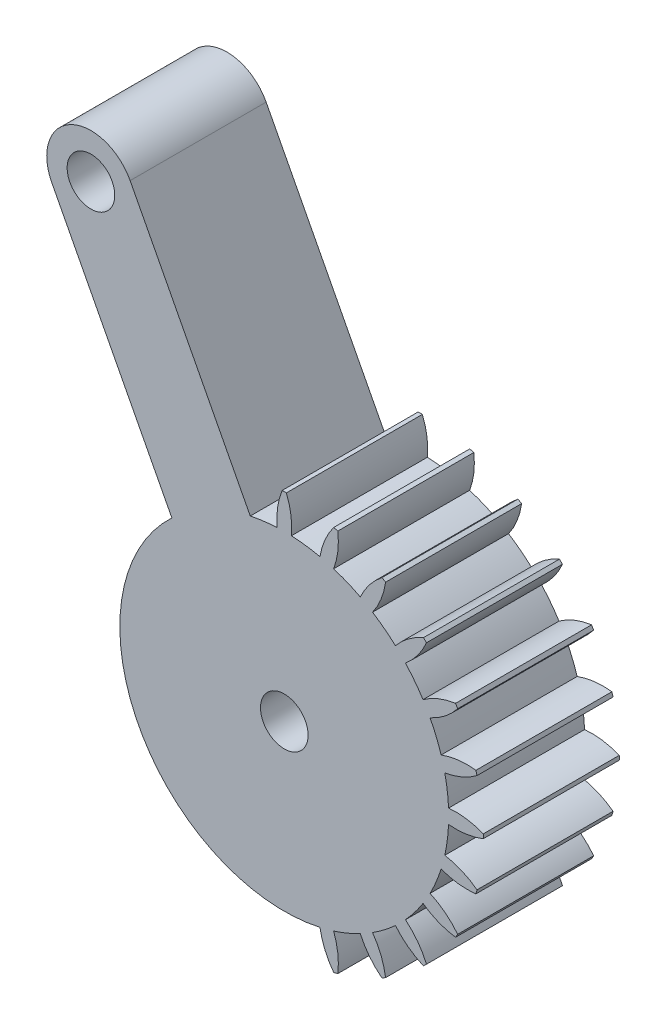
SolidWorks part; units mm, degrees
ref_plane "Front Plane" through (0, 0, 0) normal (0, 0, 1) x (1, 0, 0)
ref_plane "Top Plane" through (0, 0, 0) normal (0, 1, 0) x (1, 0, 0)
ref_plane "Right Plane" through (0, 0, 0) normal (1, 0, 0) x (0, 0, -1)
sketch "Sketch1" plane through (0, 0, 0) normal (0, 0, 1) x (1, 0, 0)
  line L0 (0, 0) -> (0, 16.3128) construction
  line L1 (0.155, 14.63) -> (-0.155, 14.63)
  line L2 (0, 0) -> (-14.3268, 27.4806) construction
  line L3 (3.9362, 14.0914) -> (3.6368, 14.1716)
  line L4 (7.4492, 12.5925) -> (7.1808, 12.7475)
  line L5 (10.4546, 10.2354) -> (10.2354, 10.4546)
  line L6 (12.7475, 7.1808) -> (12.5925, 7.4492)
  line L7 (14.1716, 3.6368) -> (14.0914, 3.9362)
  line L8 (14.63, -0.155) -> (14.63, 0.155)
  line L9 (14.0914, -3.9362) -> (14.1716, -3.6368)
  line L10 (12.5925, -7.4492) -> (12.7475, -7.1808)
  line L11 (10.2354, -10.4546) -> (10.4546, -10.2354)
  line L12 (7.1808, -12.7475) -> (7.4492, -12.5925)
  line L13 (3.6368, -14.1716) -> (3.9362, -14.0914)
  line L14 (0, 0) -> (0.52, 12.0788) construction
  line L15 (0, 0) -> (3.6285, 11.5327) construction
  line L16 (-2.5015, 11.8284) -> (-11.3335, 28.7694)
  line L17 (-8.2652, 8.8235) -> (-17.0973, 25.7645)
  circle A0 centre (0, 0) radius 1.75
  arc A1 (-8.2652, 8.8235) -> (2.6239, -11.8018) centre (0, 0) ccw
  arc A2 (-11.3335, 28.7694) -> (-17.0973, 25.7645) centre (-14.2154, 27.2669) ccw
  circle A3 centre (-14.2154, 27.2669) radius 1.75
  arc A4 (-0.155, 14.63) -> (-0.52, 12.0788) centre (4.8536, 12.6117) ccw
  arc A5 (0.155, 14.63) -> (0.52, 12.0788) centre (-4.8536, 12.6117) cw
  arc A6 (3.9362, 14.0914) -> (3.6285, 11.5327) centre (-1.4241, 13.4382) cw
  arc A7 (3.6368, 14.1716) -> (2.6239, 11.8018) centre (7.9524, 10.9258) ccw
  arc A8 (7.4492, 12.5925) -> (6.4897, 10.2006) centre (2.1025, 13.3489) cw
  arc A9 (7.1808, 12.7475) -> (5.5891, 10.7206) centre (10.5092, 8.4952) ccw
  arc A10 (10.4546, 10.2354) -> (8.9087, 8.1733) centre (5.4858, 12.3499) cw
  arc A11 (10.2354, 10.4546) -> (8.1733, 8.9087) centre (12.3499, 5.4858) ccw
  arc A12 (12.7475, 7.1808) -> (10.7206, 5.5891) centre (8.4952, 10.5092) cw
  arc A13 (12.5925, 7.4492) -> (10.2006, 6.4897) centre (13.3489, 2.1025) ccw
  arc A14 (14.1716, 3.6368) -> (11.8018, 2.6239) centre (10.9258, 7.9524) cw
  arc A15 (14.0914, 3.9362) -> (11.5327, 3.6285) centre (13.4382, -1.4241) ccw
  arc A16 (14.63, -0.155) -> (12.0788, -0.52) centre (12.6117, 4.8536) cw
  arc A17 (14.63, 0.155) -> (12.0788, 0.52) centre (12.6117, -4.8536) ccw
  arc A18 (14.0914, -3.9362) -> (11.5327, -3.6285) centre (13.4382, 1.4241) cw
  arc A19 (14.1716, -3.6368) -> (11.8018, -2.6239) centre (10.9258, -7.9524) ccw
  arc A20 (12.5925, -7.4492) -> (10.2006, -6.4897) centre (13.3489, -2.1025) cw
  arc A21 (12.7475, -7.1808) -> (10.7206, -5.5891) centre (8.4952, -10.5092) ccw
  arc A22 (10.2354, -10.4546) -> (8.1733, -8.9087) centre (12.3499, -5.4858) cw
  arc A23 (10.4546, -10.2354) -> (8.9087, -8.1733) centre (5.4858, -12.3499) ccw
  arc A24 (7.1808, -12.7475) -> (5.5891, -10.7206) centre (10.5092, -8.4952) cw
  arc A25 (7.4492, -12.5925) -> (6.4897, -10.2006) centre (2.1025, -13.3489) ccw
  arc A26 (3.6368, -14.1716) -> (2.6239, -11.8018) centre (7.9524, -10.9258) cw
  arc A27 (3.9362, -14.0914) -> (3.6285, -11.5327) centre (-1.4241, -13.4382) ccw
  arc A28 (-0.52, 12.0788) -> (-2.5015, 11.8284) centre (0, 0) ccw
  arc A29 (2.6239, 11.8018) -> (0.52, 12.0788) centre (0, 0) ccw
  arc A30 (5.5891, 10.7206) -> (3.6285, 11.5327) centre (0, 0) ccw
  arc A31 (8.1733, 8.9087) -> (6.4897, 10.2006) centre (0, 0) ccw
  arc A32 (10.2006, 6.4897) -> (8.9087, 8.1733) centre (0, 0) ccw
  arc A33 (11.5327, 3.6285) -> (10.7206, 5.5891) centre (0, 0) ccw
  arc A34 (12.0788, 0.52) -> (11.8018, 2.6239) centre (0, 0) ccw
  arc A35 (11.8018, -2.6239) -> (12.0788, -0.52) centre (0, 0) ccw
  arc A36 (10.7206, -5.5891) -> (11.5327, -3.6285) centre (0, 0) ccw
  arc A37 (8.9087, -8.1733) -> (10.2006, -6.4897) centre (0, 0) ccw
  arc A38 (6.4897, -10.2006) -> (8.1733, -8.9087) centre (0, 0) ccw
  arc A39 (3.6285, -11.5327) -> (5.5891, -10.7206) centre (0, 0) ccw
  point P13 (0, 14.63)
  dimension "D1" = 3.5
  dimension "D2" = 24.18
  dimension "D3" = 6.5
  dimension "D4" = 3.5
  dimension "D8" = 5.4
  dimension "D5" = 45
  dimension "D6" = 0.31
  dimension "D7" = 1.04
  dimension "D9" = 14.63
  dimension "D11" = 15
  dimension "D12" = 30.75
  dimension "D10" = 12
extrude "Boss-Extrude1" add sketch "Sketch1" against normal blind 10
